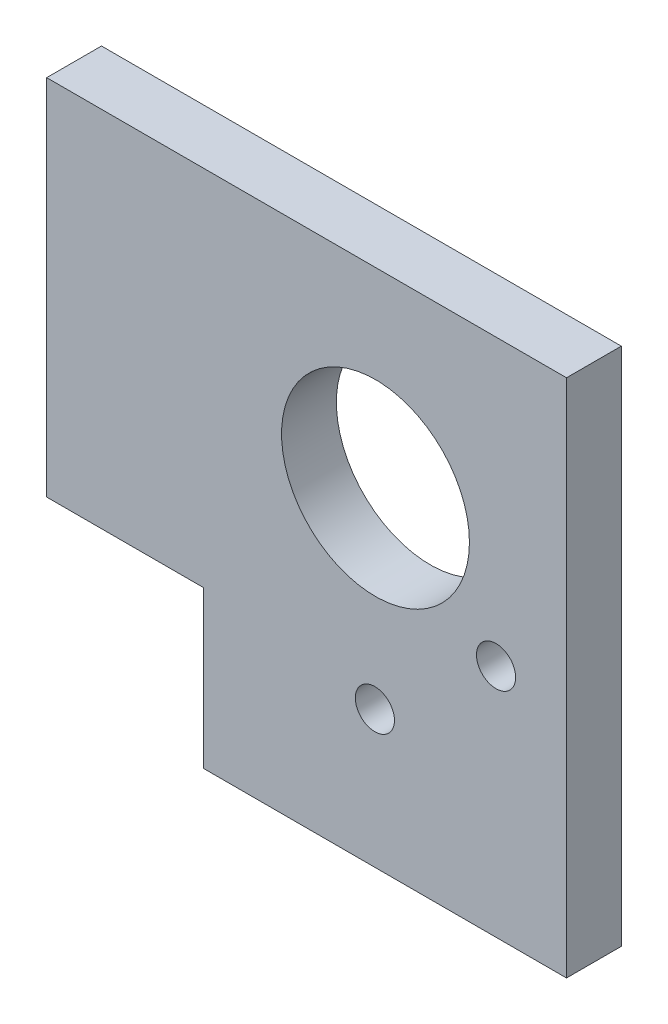
SolidWorks part; units mm, degrees
ref_plane "Front Plane" through (0, 0, 0) normal (0, 0, 1) x (1, 0, 0)
ref_plane "Top Plane" through (0, 0, 0) normal (0, 1, 0) x (1, 0, 0)
ref_plane "Right Plane" through (0, 0, 0) normal (1, 0, 0) x (0, 0, -1)
sketch "Sketch1" plane through (0, 0, 0) normal (0, 0, 1) x (1, 0, 0)
  line L0 (0, 24.4) -> (24.4, 24.4)
  line L1 (24.4, 24.4) -> (24.4, -42)
  line L2 (398, -42) -> (-22, -42) construction
  line L3 (24.4, -42) -> (-22, -42)
  line L4 (-22, -42) -> (-22, -22)
  line L5 (-22, -22) -> (-42, -22)
  line L6 (-42, -22) -> (-42, 24.4)
  line L7 (-42, -22) -> (-42, 398) construction
  line L8 (-42, 24.4) -> (0, 24.4)
  line L9 (17.0402, 21) -> (-17.0402, 21) construction
  line L10 (21, -17.0445) -> (21, 17.0402) construction
  dimension "D1" = 3.4
  dimension "D2" = 3.4
extrude "Boss-Extrude1" add sketch "Sketch1" along normal blind 7
sketch "Sketch2" plane through (0, 0, 7) normal (0, 0, 1) x (1, 0, 0)
  circle A0 centre (0, 0) radius 12
  dimension "D1" = 24
extrude "Cut-Extrude1" cut sketch "Sketch2" against normal through all
sketch "Sketch3" plane through (0, 0, 7) normal (0, 0, 1) x (1, 0, 0)
  line L0 (0, 0) -> (0, -42) construction
  line L1 (-22, -42) -> (24.4, -42) construction
  circle A1 centre (-0.076, -24.5) radius 2.5
  circle A2 centre (15.4, -12) radius 2.5
  dimension "D1" = 5
extrude "Cut-Extrude2" cut sketch "Sketch3" against normal through all
